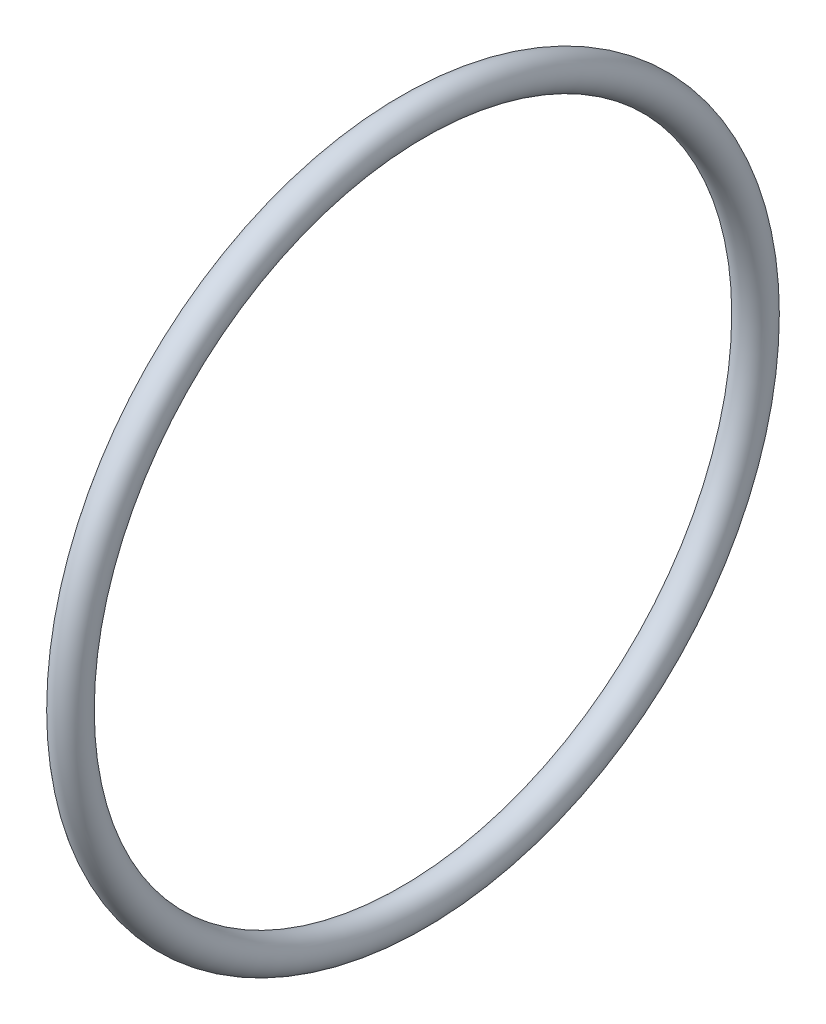
SolidWorks part; units mm, degrees
ref_plane "plan de coupe" through (0, 0, 0) normal (0, 0, 1) x (1, 0, 0)
ref_plane "Plane2" through (0, 0, 0) normal (0, 1, 0) x (1, 0, 0)
ref_plane "Plane3" through (0, 0, 0) normal (1, 0, 0) x (0, 0, -1)
sketch "Esquisse1" plane through (0, 0, 0) normal (0, 0, 1) x (1, 0, 0)
  circle A0 centre (0, 0) radius 0.75
  dimension "D1" = 1.5
sketch "Esquisse2" plane through (0, 0, 0) normal (1, 0, 0) x (0, 0, -1)
  circle A0 centre (0, -15.25) radius 14.5
  dimension "D1" = 29
sweep "joint" add profiles "Esquisse1" path "Esquisse2"
ref_plane "Plan4" through (0, -15.25, 0) normal (0, 1, 0) x (-1, 0, 0)
ref_axis "Axe3" through (-50, -15.25, 0) along (1, 0, 0)
